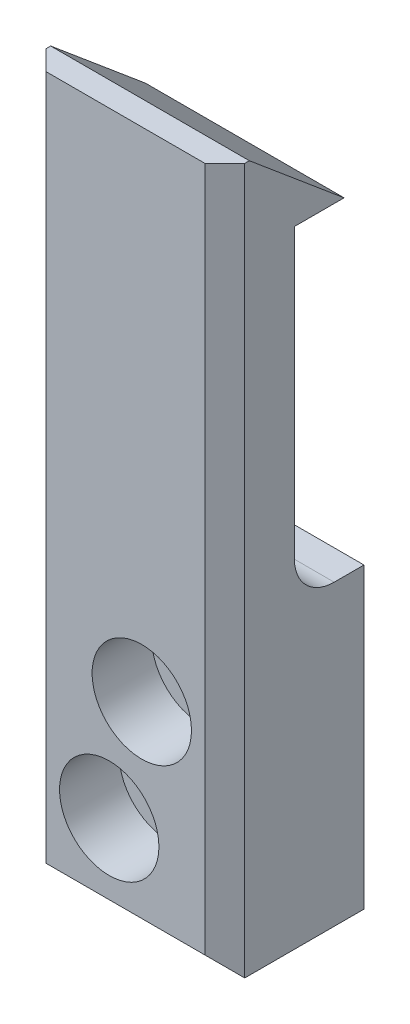
SolidWorks part; units mm, degrees
ref_plane "前视基准面" through (0, 0, 0) normal (0, 0, 1) x (1, 0, 0)
ref_plane "上视基准面" through (0, 0, 0) normal (0, 1, 0) x (1, 0, 0)
ref_plane "右视基准面" through (0, 0, 0) normal (1, 0, 0) x (0, 0, -1)
ref_plane "基准面4" through (3, 0, 0) normal (1, 0, 0) x (0, 0, -1)
sketch "草图3" plane through (3, 0, 0) normal (1, 0, 0) x (0, 0, -1)
  line L0 (0, -25.4015) -> (-7, -25.4015)
  line L1 (-7, -25.4015) -> (-7, 11.1331)
  line L2 (-7, 11.1331) -> (-1, 6.0985)
  line L3 (-1, 6.0985) -> (-3.5, 6.0985)
  line L4 (-3.5, 6.0985) -> (-3.5, -8.4015)
  line L5 (-1.5, -10.4015) -> (0, -10.4015)
  line L6 (0, -10.4015) -> (0, -25.4015)
  line L7 (144.1721, 5.5985) -> (-3, 5.5985) construction
  line L8 (-3, 2.0985) -> (-3, 5.5985) construction
  line L9 (-5.767, 10.0985) -> (-7, 10.0985)
  line L10 (143.6721, -25.4015) -> (0, -25.4015) construction
  line L11 (114.9329, -10.4015) -> (0, -10.4015) construction
  arc A0 (-3.5, -8.4015) -> (-1.5, -10.4015) centre (-1.5, -8.4015) ccw
  point P17 (0, 0)
  dimension "D7" = 2
  dimension "D1" = 0.5
  dimension "D2" = 0.5
  dimension "D3" = 2
  dimension "D4" = 3.5
  dimension "D5" = 40
  dimension "D6" = 4
extrude "凸台-拉伸1" add sketch "草图3" against normal blind 10 contours A0 L4 L3 L2 L9 L1 L0 L6 L5 region at (3, -10.679, 4.1815)
sketch "Sketch2" plane through (0, 0, 0) normal (0, 0, -1) x (-1, 0, 0)
  line L0 (2, -25.4015) -> (2, -10.4015) construction
  line L1 (7, -25.4015) -> (-3, -25.4015) construction
  line L2 (7, -10.4015) -> (-3, -10.4015) construction
  line L3 (7, -17.9015) -> (-3, -17.9015) construction
  line L4 (7, -10.4015) -> (7, -25.4015) construction
  line L6 (2.8188, -14.9563) -> (1.1812, -14.9563) construction
  line L7 (2.8188, -14.9563) -> (2.8188, -20.8468) construction
  line L8 (-3, -10.4015) -> (-3, -25.4015) construction
  line L9 (2.8188, -20.8468) -> (1.1812, -20.8468) construction
  line L10 (1.1812, -14.9563) -> (1.1812, -20.8468) construction
  line L11 (2.8188, -14.9563) -> (1.1812, -20.8468) construction
  line L12 (2.8188, -20.8468) -> (1.1812, -14.9563) construction
  circle A0 centre (2.8188, -20.8468) radius 0.8 construction
  circle A1 centre (1.1812, -14.9563) radius 1 construction
  point P6 (2, -17.9015)
  point P8 (2, -17.9015)
  point P20 (0.8736, -14.9654)
  point P21 (1.1812, -14.9563)
sketch "Sketch4" plane through (0, 0, 7) normal (0, 0, 1) x (1, 0, 0)
  point P0 (-2.8188, -20.8468)
  point P2 (-1.1812, -14.9563)
hole_wizard "Hole4" positions "Sketch7" profile "Sketch8" legacy end condition through all
sketch "Sketch7" plane through (0, 0, 7) normal (0, 0, 1) x (1, 0, 0)
  point P0 (-2.8188, -20.8468)
  point P3 (-1.1812, -14.9563)
sketch "Sketch8" plane through (-2.8188, -20.8468, 7) normal (1, 0, 0) x (0, -1, 0)
  line L0 (0, 0) -> (0, 7.4807)
  line L1 (0, 7.4807) -> (0.8, 7)
  line L2 (0.8, 7) -> (0.8, 3)
  line L3 (0.8, 3) -> (2.5, 3)
  line L4 (2.5, 0) -> (0, 0)
  line L5 (0, -11.3109) -> (0, 121.1557) construction
  line L6 (0, 7.4807) -> (-0.8, 7) construction
  line L7 (2.5, 3) -> (2.5, 0)
  dimension "Depth" = 7
  dimension "Drill Angle" = 118
  dimension "Diameter" = 1.6
  dimension "C-Bore Diameter" = 5
  dimension "C-Bore Depth" = 3
chamfer "倒角1" distance 1 angle 45 3 edges at (-7, -7.6515, 7) (3, -7.6515, 7) (-2, -25.4015, 7)
